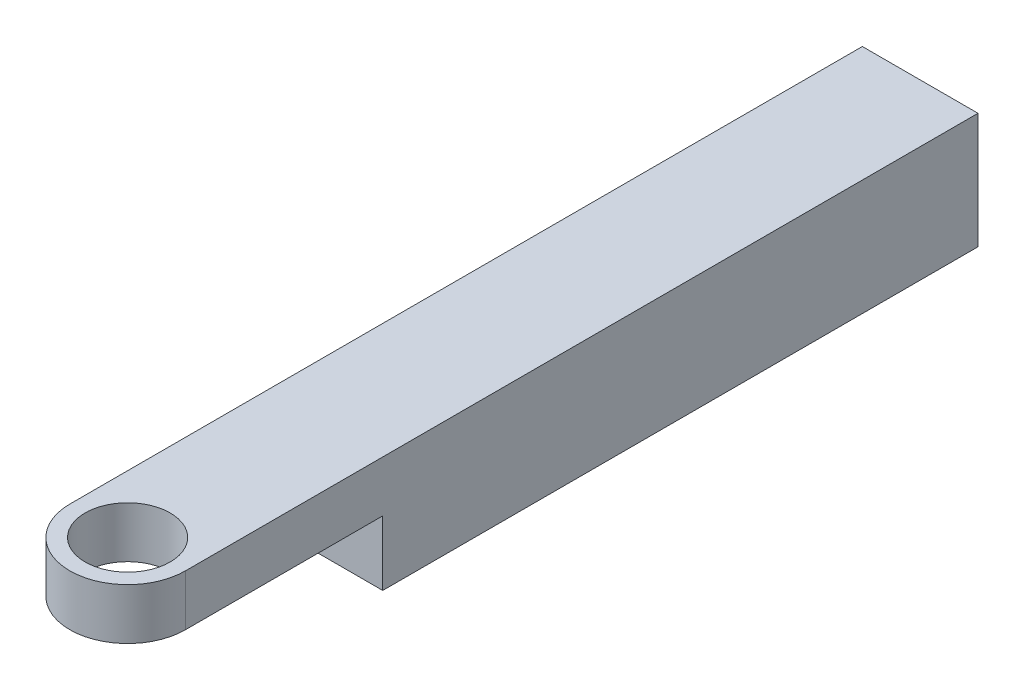
SolidWorks part; units mm, degrees
material "ABS"
ref_plane "Front Plane" through (0, 0, 0) normal (0, 0, 1) x (1, 0, 0)
ref_plane "Top Plane" through (0, 0, 0) normal (0, 1, 0) x (1, 0, 0)
ref_plane "Right Plane" through (0, 0, 0) normal (1, 0, 0) x (0, 0, -1)
sketch "Sketch1" plane through (0, 0, 0) normal (0, 0, 1) x (1, 0, 0)
  line L1 (0, 0) -> (-6.8, 0)
  line L2 (0, 0) -> (0, 6.8)
  line L3 (0, 6.8) -> (-6.8, 6.8)
  line L4 (-6.8, 0) -> (-6.8, 6.8)
  circle A0 centre (-3.4, 3.4) radius 1.75
  dimension "D3" = 3.5
  dimension "D4" = 3.4
  dimension "D5" = 3.4
  dimension "D1" = 6.8
  dimension "D2" = 6.8
extrude "Boss-Extrude1" add sketch "Sketch1" along normal blind 50
sketch "Sketch2" plane through (0, 0, 0) normal (0, 0, -1) x (-1, 0, 0)
  line L1 (6.5754, 3.4) -> (4.9877, 6.15)
  line L2 (4.9877, 6.15) -> (1.8123, 6.15)
  line L3 (1.8123, 6.15) -> (0.2246, 3.4)
  line L4 (0.2246, 3.4) -> (1.8123, 0.65)
  line L5 (1.8123, 0.65) -> (4.9877, 0.65)
  line L6 (4.9877, 0.65) -> (6.5754, 3.4)
  line L7 (0, 0) -> (0, 6.8) construction
  circle A0 centre (3.4, 3.4) radius 2.75 construction
  dimension "D1" = 5.5
  dimension "D2" = 3.4
extrude "Cut-Extrude1" cut sketch "Sketch2" against normal blind 8
sketch "Sketch5" plane through (0, 0, 50) normal (0, 0, 1) x (1, 0, 0)
  line L1 (0, 6.8) -> (-6.8, 6.8)
  line L2 (0, 6.8) -> (0, 0)
  line L3 (0, 0) -> (-6.8, 0)
  line L4 (-6.8, 6.8) -> (-6.8, 0)
  dimension "D1" = 6.8
  dimension "D2" = 6.8
extrude "Boss-Extrude2" add sketch "Sketch5" against normal blind 7
sketch "Sketch3" plane through (0, 0, 50) normal (0, 0, 1) x (1, 0, 0)
  line L6 (-6.8, 6.8) -> (-6.8, 0) construction
  line L7 (0, 0) -> (-6.8, 0)
  line L8 (0, 0) -> (0, 3.8)
  line L9 (0, 3.8) -> (-6.8, 3.8)
  line L10 (-6.8, 0) -> (-6.8, 3.8)
  line L11 (0, 6.8) -> (-6.8, 6.8) construction
  dimension "D1" = 3
extrude "Cut-Extrude2" cut sketch "Sketch3" against normal blind 15
sketch "Sketch4" plane through (0, 3.8, 0) normal (0, -1, 0) x (1, 0, 0)
  line L0 (0, 35) -> (0, 50) construction
  line L1 (0, 50) -> (-6.8, 50) construction
  circle A0 centre (-3.4, 46.6) radius 2.5
  dimension "D1" = 5
  dimension "D2" = 3.4
  dimension "D3" = 3.4
extrude "Cut-Extrude3" cut sketch "Sketch4" against normal blind 20
fillet "Fillet3" 2 edges at (-6.8, 5.3, 50) (0, 5.3, 50) type full round first side face at (-6.8, 3.5333, 28.3333) second side face at (0, 3.5333, 28.3333) middle face at (-3.4, 5.3, 50)
